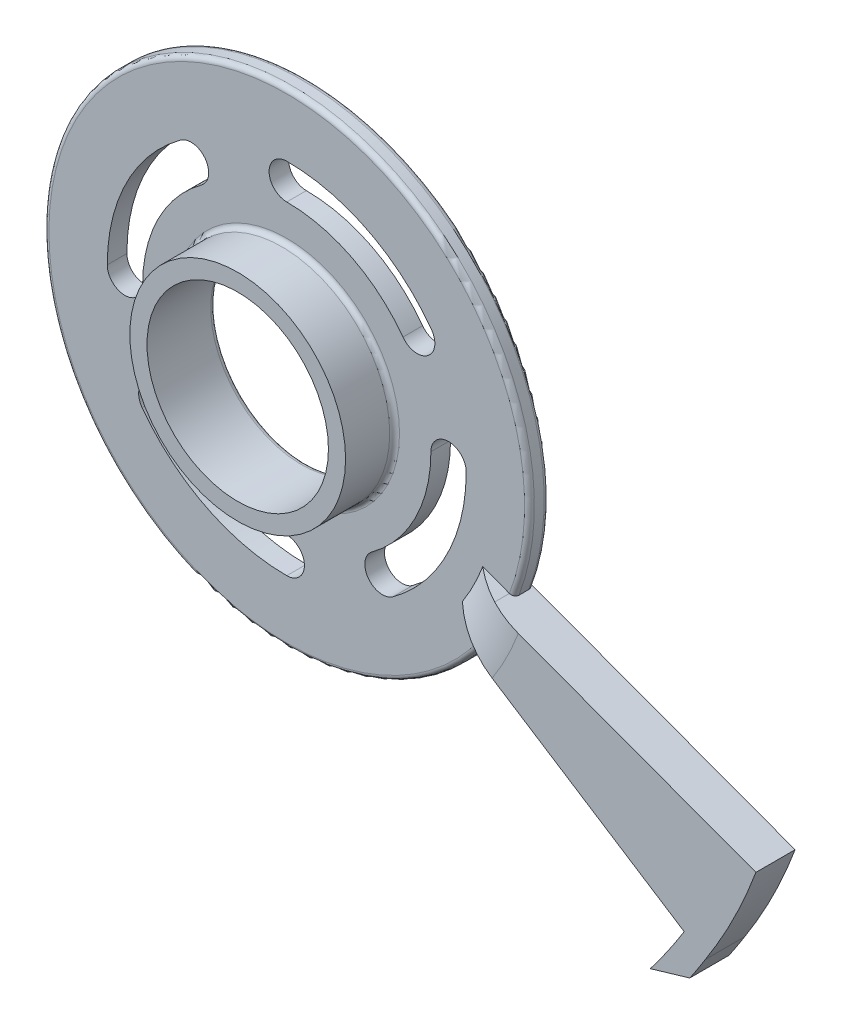
SolidWorks part; units mm, degrees
ref_plane "Front Plane" through (0, 0, 0) normal (0, 0, 1) x (1, 0, 0)
ref_plane "Top Plane" through (0, 0, 0) normal (0, 1, 0) x (1, 0, 0)
ref_plane "Right Plane" through (0, 0, 0) normal (1, 0, 0) x (0, 0, -1)
sketch "Sketch3" plane through (0, 0, 0) normal (0, 0, 1) x (1, 0, 0)
  circle A0 centre (0, 0) radius 24.75
  dimension "D1" = 49.5
extrude "Boss-Extrude3" add sketch "Sketch3" along normal blind 2
sketch "Sketch4" plane through (0, 0, 2) normal (0, 0, 1) x (1, 0, 0)
  line L0 (0, 0) -> (0, 16.5) construction
  line L1 (0, 0) -> (16.5, 0) construction
  line L2 (0, 0) -> (0, -16.5) construction
  line L3 (0, 0) -> (-16.5, 0) construction
  line L4 (0, 0) -> (-1.8, 16.5) construction
  line L5 (0, 0) -> (26.559, 15.3436) construction
  line L6 (6.6418, 13.114) -> (0, 0) construction
  line L7 (0, 0) -> (1.8, -16.5) construction
  line L8 (0, 0) -> (-16.5, -1.8) construction
  line L9 (-16.5, -1.8) -> (16.5, 1.8) construction
  line L10 (0, 0) -> (-17.9121, -10.3482) construction
  line L11 (0, 0) -> (3.6768, 7.2596) construction
  line L12 (3.6768, 7.2596) -> (-9.2683, -18.3) construction
  line L13 (0, 0) -> (14.495, -7.3412) construction
  arc A0 (-14.7, 0) -> (-18.3, 0) centre (-16.5, 0) cw
  arc A1 (0, -14.7) -> (0, -18.3) centre (0, -16.5) cw
  arc A2 (14.7, 0) -> (18.3, 0) centre (16.5, 0) cw
  arc A3 (0, 14.7) -> (0, 18.3) centre (0, 16.5) cw
  arc A4 (0, 14.7) -> (11.8504, 8.6982) centre (0, 0) cw
  arc A5 (0, 18.3) -> (14.7525, 10.8284) centre (0, 0) cw
  arc A8 (11.8504, 8.6982) -> (14.7525, 10.8284) centre (13.3014, 9.7633) ccw
  arc A9 (-11.8504, -8.6982) -> (0, -14.7) centre (0, 0) ccw
  arc A10 (-11.8504, -8.6982) -> (-14.7525, -10.8284) centre (-13.3014, -9.7633) ccw
  arc A11 (-14.7525, -10.8284) -> (0, -18.3) centre (0, 0) ccw
  arc A12 (14.7, 0) -> (8.6982, -11.8504) centre (0, 0) cw
  arc A13 (18.3, 0) -> (10.8284, -14.7525) centre (0, 0) cw
  arc A15 (8.6982, -11.8504) -> (10.8284, -14.7525) centre (9.7633, -13.3014) ccw
  arc A16 (-8.6982, 11.8504) -> (-10.8284, 14.7525) centre (-9.7633, 13.3014) ccw
  arc A17 (-8.6982, 11.8504) -> (-14.7, 0) centre (0, 0) ccw
  arc A18 (-10.8284, 14.7525) -> (-18.3, 0) centre (0, 0) ccw
  point P24 (13.3014, 9.7633)
  dimension "D5" = 1.8
  dimension "D8" = 1.8
  dimension "D1" = 33.086
  dimension "D2" = 33.086
  dimension "D9" = 66.21
sketch "Sketch7" plane through (0, 0, 2) normal (0, 0, 1) x (1, 0, 0)
  circle A0 centre (0, 0) radius 9.25
  dimension "D1" = 18.5
extrude "Cut-Extrude2" cut sketch "Sketch7" against normal blind 2
sketch "Sketch8" plane through (0, 0, 2) normal (0, 0, 1) x (1, 0, 0)
  circle A0 centre (0, 0) radius 9.25
  circle A1 centre (0, 0) radius 11
  dimension "D1" = 22
extrude "Boss-Extrude6" add sketch "Sketch8" along normal blind 5
fillet "Fillet31" radius 0.5 2 edges at (24.75, 0, 0) (9.25, 0, 0)
fillet "Fillet32" radius 0.5 2 edges at (11, 0, 2) (24.75, 0, 2)
extrude "Cut-Extrude7" cut sketch "Sketch4" against normal blind 2
sketch "Sketch13" plane through (0, 0, 2) normal (0, 0, 1) x (1, 0, 0)
  line L0 (29.1522, -10.8744) -> (18.0573, -6.8219) construction
  line L1 (47.1954, -17.6049) -> (23.4234, -8.7374) construction
  line L2 (38.8195, -30.3981) -> (19.8773, -13.8908)
  line L3 (22.7043, -8.5193) -> (47.1954, -17.6049)
  arc A0 (22.7043, -8.5193) -> (19.8773, -13.8908) centre (0, 0) cw
  circle A1 centre (0, 0) radius 24.25 construction
  arc A2 (38.8195, -30.3981) -> (47.1954, -17.6049) centre (-5.9397, 8.0449) ccw
  arc A3 (2.9301, -50.2867) -> (47.1954, -17.6049) centre (-5.9397, 8.0449) ccw construction
extrude "Boss-Extrude8" add sketch "Sketch13" along normal blind 2 and the other way blind 2
sketch "Sketch14" plane through (0, 0, 4) normal (0, 0, 1) x (1, 0, 0)
  line L0 (47.1954, -17.6049) -> (0, 0) construction
  line L1 (0, 0) -> (56.1975, -36.1151) construction
  line L2 (19.8506, -13.868) -> (38.8195, -30.3981)
  line L3 (41.6833, -26.7876) -> (20.3711, -13.0914)
  arc A0 (38.8195, -30.3981) -> (41.6833, -26.7876) centre (-5.9397, 8.0449) ccw
  arc A1 (38.8195, -30.3981) -> (47.1954, -17.6049) centre (-5.9397, 8.0449) ccw construction
  arc A3 (20.3711, -13.0914) -> (19.8506, -13.868) centre (0, 0) cw
  dimension "D1" = 12.27
extrude "Cut-Extrude9" cut sketch "Sketch14" against normal blind 2
sketch "Sketch15" plane through (0, 0, 2) normal (0, 0, 1) x (1, 0, 0)
  line L0 (38.8195, -30.3981) -> (20.2564, -14.2211)
  line L1 (41.6833, -26.7876) -> (20.7651, -13.4675)
  arc A1 (38.8195, -30.3981) -> (41.6833, -26.7876) centre (-5.9397, 8.0449) ccw construction
  arc A2 (41.6833, -26.7876) -> (38.8195, -30.3981) centre (-5.9397, 8.0449) cw
  arc A3 (20.2564, -14.2211) -> (20.7651, -13.4675) centre (0, 0) ccw
extrude "Cut-Extrude10" cut sketch "Sketch15" against normal blind 2
fillet "Fillet33" radius 0.5 1 edges at (20.5142, -13.8467, 2)
fillet "Fillet34" radius 0.5 1 edges at (20.5142, -13.8467, 0)
sketch "Sketch16" plane through (0, 0, 0) normal (0, 0, -1) x (-1, 0, 0)
  line L0 (-47.1954, -17.6049) -> (-22.7043, -8.5193) construction
  line L2 (-46.7688, -17.4467) -> (-47.1954, -17.6049)
  arc A0 (-44.6482, -22.3216) -> (-46.7688, -17.4467) centre (0, 0) cw
  arc A1 (-47.1954, -17.6049) -> (-41.6833, -26.7876) centre (5.9397, 8.0449) ccw construction
  arc A3 (-47.1954, -17.6049) -> (-44.6482, -22.3216) centre (5.9397, 8.0449) ccw
extrude "Cut-Extrude11" cut sketch "Sketch16" against normal blind 4
sketch "Sketch17" plane through (0, 0, 0) normal (0, 0, -1) x (-1, 0, 0)
  line L0 (-41.6833, -26.7876) -> (-20.4005, -13.1103) construction
  line L1 (-41.6803, -26.7856) -> (-40.7878, -26.2121) construction
  line L2 (-41.6803, -26.7856) -> (-41.9932, -26.9867)
  arc A0 (-44.6482, -22.3216) -> (-41.9932, -26.9867) centre (0, 0) ccw
  arc A4 (-44.6482, -22.3216) -> (-41.6803, -26.7856) centre (5.906, 8.0697) ccw
extrude "Boss-Extrude10" add sketch "Sketch17" against normal blind 4
sketch "Sketch18" plane through (0, 0, 4) normal (0, 0, 1) x (1, 0, 0)
  line L4 (41.9932, -26.9867) -> (20.4005, -13.1103) construction
  line L5 (41.9932, -26.9867) -> (44.7423, -28.7534)
  line L7 (43.1591, -16.1075) -> (51.7387, -19.2904) construction
  line L8 (46.7688, -17.4467) -> (22.7043, -8.5193) construction
  line L9 (49.8306, -18.5888) -> (46.7688, -17.4467)
  arc A0 (49.8306, -18.5888) -> (44.7423, -28.7534) centre (0, 0) cw
  arc A4 (41.9932, -26.9867) -> (46.7688, -17.4467) centre (0, 0) ccw
extrude "Boss-Extrude14" add sketch "Sketch18" against normal blind 4
sketch "Sketch23" plane through (0, 0, 0) normal (0, 0, -1) x (-1, 0, 0)
  line L2 (-22.7052, -8.5167) -> (-49.8336, -18.5807)
  line L3 (-20.3362, -13.2099) -> (-44.6781, -28.8531)
  line L4 (-44.7423, -28.7534) -> (-41.6833, -26.7876) construction
  line L5 (-46.7688, -17.4467) -> (-22.7043, -8.5193) construction
  arc A4 (-22.7052, -8.5167) -> (-20.3362, -13.2099) centre (0, 0) ccw
  arc A5 (-19.8773, -13.8908) -> (-22.7043, -8.5193) centre (0, 0) ccw construction
  arc A6 (-20.3433, -13.199) -> (-19.8773, -13.8908) centre (0, 0) ccw construction
  arc A7 (-44.6781, -28.8531) -> (-49.8336, -18.5807) centre (0, 0) cw
extrude "Boss-Extrude16" add sketch "Sketch23" against normal blind 4
sketch "Sketch24" plane through (0, 0, 2) normal (0, 0, 1) x (1, 0, 0)
  line L0 (44.6781, -28.8531) -> (20.3362, -13.2099) construction
  line L1 (22.7052, -8.5167) -> (0, 0) construction
  line L2 (0, 0) -> (20.3362, -13.2099) construction
  line L3 (22.7052, -8.5167) -> (19.9895, -7.498)
  line L4 (17.9038, -11.6298) -> (20.3362, -13.2099)
  arc A0 (22.7052, -8.5167) -> (20.3362, -13.2099) centre (0, 0) cw
  arc A1 (17.9038, -11.6298) -> (19.9895, -7.498) centre (0, 0) ccw
extrude "Boss-Extrude18" add sketch "Sketch24" along normal blind 2
fillet "Fillet36" radius 10 1 edges at (19.0589, -9.6206, 4)
sketch "Sketch25" plane through (0, 0, 4) normal (0, 0, 1) x (1, 0, 0)
  line L2 (47.5342, -23.8566) -> (-9.2361, 4.6355) construction
  line L5 (44.6781, -28.8531) -> (22.9437, -14.8855) construction
  line L6 (43.0934, -31.279) -> (39.0664, -32.47)
  line L7 (42.5251, -27.4694) -> (44.6781, -28.8531)
  arc A0 (44.6781, -28.8531) -> (49.8336, -18.5807) centre (0, 0) ccw construction
  arc A2 (44.6781, -28.8531) -> (43.0934, -31.279) centre (-9.2361, 4.6355) cw
  arc A3 (42.5251, -27.4694) -> (39.0664, -32.47) centre (-9.2361, 4.6355) cw
extrude "Boss-Extrude22" add sketch "Sketch25" against normal blind 4
